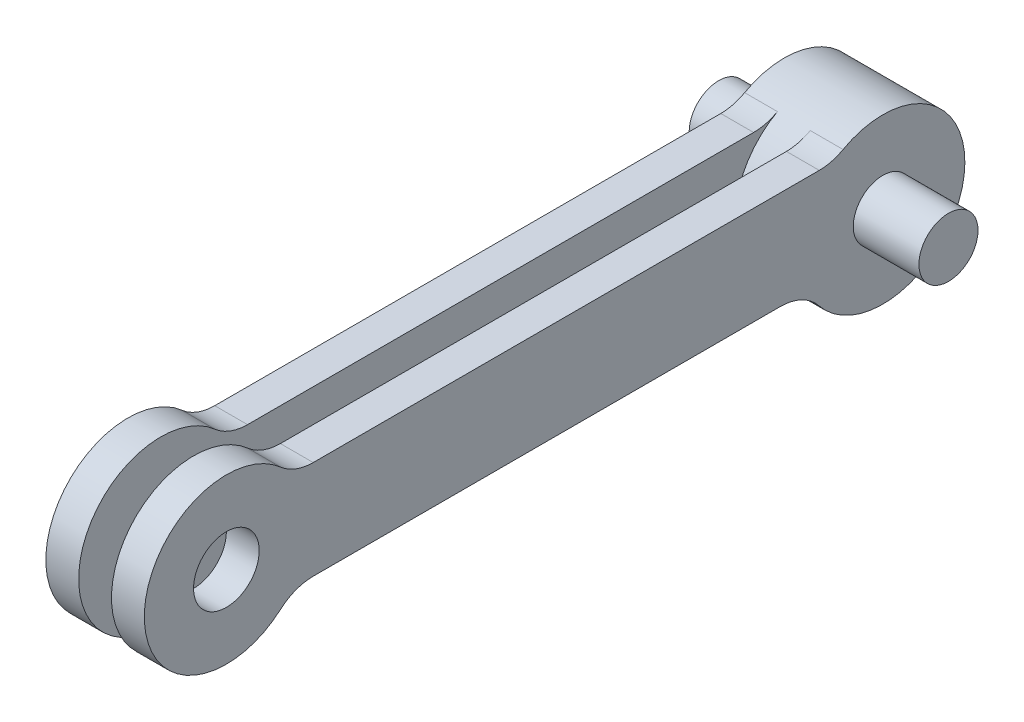
SolidWorks part; units mm, degrees
ref_plane "前视基准面" through (0, 0, 0) normal (0, 0, 1) x (1, 0, 0)
ref_plane "上视基准面" through (0, 0, 0) normal (0, 1, 0) x (1, 0, 0)
ref_plane "右视基准面" through (0, 0, 0) normal (1, 0, 0) x (0, 0, -1)
other "Configuration Table"
sketch "草图1" plane through (0, 0, 0) normal (1, 0, 0) x (0, 0, -1)
  line L1 (0, -3) -> (40, -3)
  line L2 (0, -3) -> (0, 3)
  line L3 (0, 3) -> (40, 3)
  line L4 (40, -3) -> (40, 3)
  circle A0 centre (0, 0) radius 5
  circle A1 centre (40, -1) radius 5
  circle A2 centre (0, 0) radius 2
  circle A3 centre (40, -1) radius 2
  dimension "D1" = 4
  dimension "D4" = 10
  dimension "D5" = 10
  dimension "D2" = 6
  dimension "D3" = 2
  dimension "D6" = 40
extrude "凸台-拉伸1" add sketch "草图1" along normal blind 2 contours A0 | L3 L4 L1 L2 | A1
extrude "切除-拉伸2" cut sketch "草图1<3>" against normal through all and the other way through all contours A2 | A3
sketch "草图1<3>" plane through (0, 0, 0) normal (1, 0, 0) x (0, 0, -1) same geometry as "草图1"
fillet "圆角1" radius 3 4 edges at (1, -3, -4) (1, -3, -35.4174) (1, 3, -37) (1, 3, -4)
extrude "凸台-拉伸2" add sketch "草图1<4>" against normal blind 1 contours A3 L1 A1 L3 L4 | A3 L4 L3 A1 L1 region at (0, 0.0971, -37.2585) region at (0, -3.1385, -37.7087)
sketch "草图1<4>" plane through (0, 0, 0) normal (1, 0, 0) x (0, 0, -1) same geometry as "草图1"
ref_plane "基准面1" through (-1, 0, 0) normal (-1, 0, 0) x (0, 0, 1)
mirror "镜向3" about plane through (-1, 0, 0) normal (-1, 0, 0) of bodies 108
sketch "草图2" plane through (2, 0, 0) normal (1, 0, 0) x (0, 0, -1)
  circle A0 centre (40, -1) radius 2
  circle A1 centre (40, -1) radius 1.8
  circle A2 centre (40, -1) radius 2 construction
  dimension "D1" = 3.6
extrude "凸台-拉伸3" add sketch "草图2" against normal up to surface (6 mm away) contours A0 up to face at (-4, 0, -2)
extrude "凸台-拉伸4" add sketch "草图2<3>" along normal blind 4 contours A1 region at (2, -1, -40)
sketch "草图2<3>" plane through (2, 0, 0) normal (1, 0, 0) x (0, 0, -1) same geometry as "草图2"
extrude "凸台-拉伸5" add sketch "草图2<4>" against normal blind 4 from surface contours A1 region at (2, -1, -40) starting at face at (-4, 0, -2)
sketch "草图2<4>" plane through (2, 0, 0) normal (1, 0, 0) x (0, 0, -1) same geometry as "草图2"
